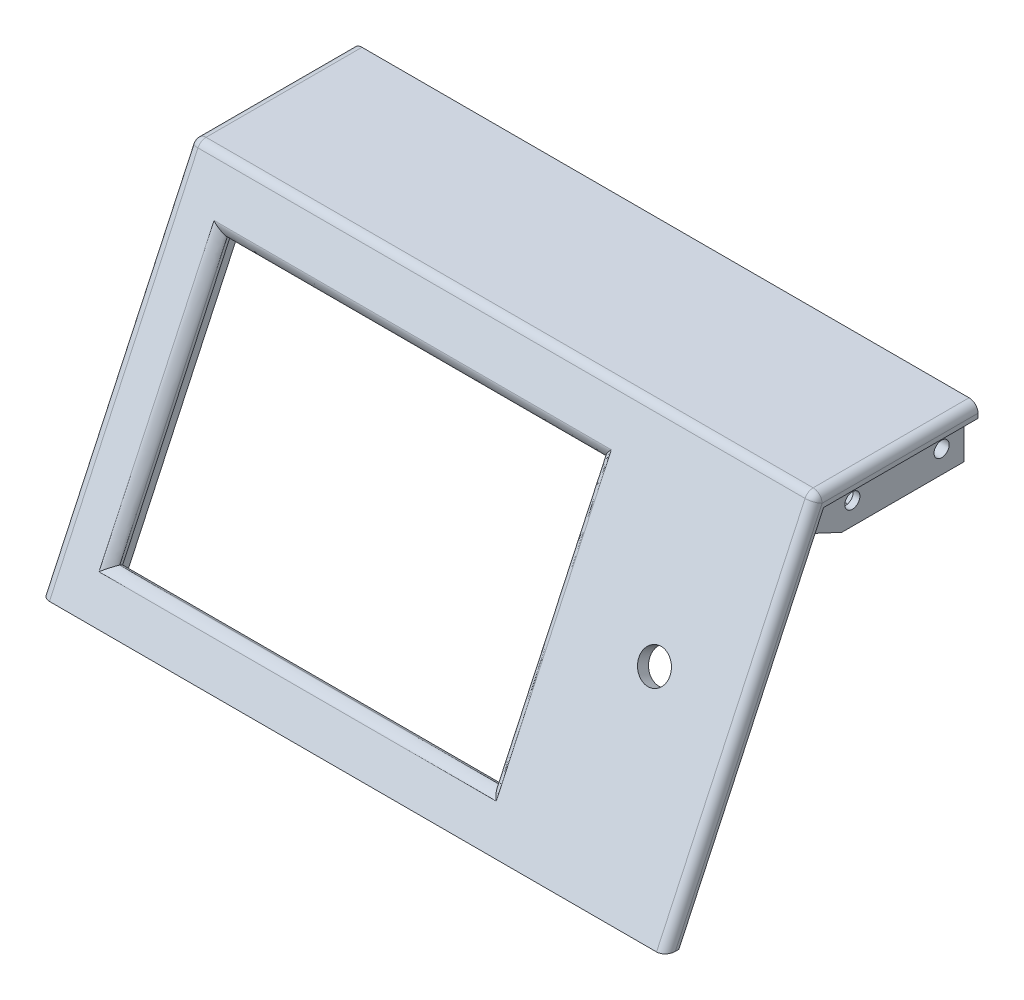
SolidWorks part; units mm, degrees
ref_plane "Piano frontale" through (0, 0, 0) normal (0, 0, 1) x (1, 0, 0)
ref_plane "Piano superiore" through (0, 0, 0) normal (0, 1, 0) x (1, 0, 0)
ref_plane "Piano destro" through (0, 0, 0) normal (1, 0, 0) x (0, 0, -1)
sketch "Schizzo5" plane through (0, 0, 0) normal (-1, 0, 0) x (0, 0, 1)
  line L0 (30.8095, -72.5046) -> (-3, 0)
  line L3 (33.8095, -72.5046) -> (30.8095, -72.5046)
  line L5 (-3, 0) -> (0, 0)
  line L6 (0, 0) -> (33.8095, -72.5046)
  line L7 (0, 0) -> (0, -3)
  line L8 (0, -3) -> (-36.2, -3)
  line L9 (-36.2, -3) -> (-36.2, 0)
  line L10 (-36.2, 0) -> (0, 0)
  dimension "D1" = 3
  dimension "D2" = 3
  dimension "D4" = 80
  dimension "D5" = 115
  dimension "D6" = 3
  dimension "D7" = 36.2
extrude "Estrusione-Estrusione3" add sketch "Schizzo5" against normal blind 140
sketch "Schizzo6" plane through (0, 0, 0) normal (0, 0.4226, 0.9063) x (1, 0, 0)
  line L0 (140, 0) -> (0, 0) construction
  line L1 (11.5, -69.5) -> (96.5, -69.5)
  line L2 (11.5, -69.5) -> (11.5, -12.5)
  line L3 (11.5, -12.5) -> (96.5, -12.5)
  line L4 (96.5, -69.5) -> (96.5, -12.5)
  line L5 (140, 0) -> (0, 0) construction
  line L6 (0, 0) -> (0, -80) construction
  line L7 (140, 0) -> (140, -80) construction
  circle A0 centre (120, -38.5) radius 3.5
  point P12 (11.5, -41)
  dimension "D5" = 7
  dimension "D7" = 20
  dimension "D1" = 85
  dimension "D2" = 57
  dimension "D3" = 41
  dimension "D4" = 11.5
  dimension "D6" = 38.5
extrude "Taglio-Estrusione1" cut sketch "Schizzo6" against normal up to next
fillet "Raccordo1" radius 2 4 edges at (96.5, -37.1586, 17.3273) (54, -62.9884, 29.372) (54, -11.3288, 5.2827) (11.5, -37.1586, 17.3273) conic rho 0.2
sketch "Schizzo8" plane through (0, -1.1491, -2.4642) normal (0, -0.4226, -0.9063) x (-1, 0, 0)
  line L0 (0, -78.7321) -> (0, -2.0423) construction
  line L1 (-114.2, -20.0423) -> (-104.2, -20.0423)
  line L2 (-114.2, -20.0423) -> (-114.2, -8.0423)
  line L3 (-114.2, -8.0423) -> (-104.2, -8.0423)
  line L4 (-104.2, -20.0423) -> (-104.2, -8.0423)
  line L5 (-96.5, -12.5) -> (-96.5, -69.5) construction
  line L7 (-114.2, -72.7321) -> (-104.2, -72.7321)
  line L8 (-114.2, -72.7321) -> (-114.2, -60.7321)
  line L9 (-114.2, -60.7321) -> (-104.2, -60.7321)
  line L10 (-104.2, -72.7321) -> (-104.2, -60.7321)
  line L11 (-11.5, -69.5) -> (-11.5, -12.5) construction
  line L12 (-3, -72.7321) -> (-9.8, -72.7321)
  line L13 (-3, -72.7321) -> (-3, -8.0423)
  line L14 (-3, -8.0423) -> (-9.8, -8.0423)
  line L15 (-9.8, -72.7321) -> (-9.8, -8.0423)
  line L17 (-140, -2.0423) -> (0, -2.0423) construction
  line L19 (-140, -78.7321) -> (0, -78.7321) construction
  dimension "D1" = 7.7
  dimension "D2" = 12
  dimension "D3" = 10
  dimension "D4" = 12
  dimension "D5" = 1.7
  dimension "D6" = 6
  dimension "D7" = 6
  dimension "D8" = 6
  dimension "D9" = 6
  dimension "D10" = 3
extrude "Estrusione-Estrusione4" add sketch "Schizzo8" along normal blind 4
sketch "Schizzo9" plane through (0, -1.1491, -2.4642) normal (0, -0.4226, -0.9063) x (-1, 0, 0)
  line L5 (-140, -78.7321) -> (0, -78.7321) construction
  line L6 (-125, -78.7321) -> (-18, -78.7321)
  line L7 (-125, -78.7321) -> (-125, -72.7321)
  line L8 (-125, -72.7321) -> (-18, -72.7321)
  line L9 (-18, -78.7321) -> (-18, -72.7321)
  line L10 (-3, -72.7321) -> (-3, -8.0423) construction
  line L12 (-140, -78.7321) -> (-140, -2.0423) construction
  point P12 (-18, -75.7321)
  dimension "D1" = 15
  dimension "D2" = 6
  dimension "D3" = 15
extrude "Estrusione-Estrusione5" add sketch "Schizzo9" along normal blind 6
sketch "Schizzo10" plane through (18, 0, 0) normal (-1, 0, 0) x (0, 0, 1)
  line L0 (30.8095, -72.5046) -> (26.1001, -74.7006)
  line L1 (25.3716, -75.0403) -> (30.8095, -72.5046) construction
  line L2 (26.1001, -74.7006) -> (29.5416, -69.7857)
  line L3 (29.5416, -69.7857) -> (30.8095, -72.5046)
  line L4 (25.3716, -75.0403) -> (22.8359, -69.6025) construction
  line L5 (30.8095, -72.5046) -> (28.2738, -67.0668) construction
  line L6 (28.2738, -67.0668) -> (24.2999, -72.742)
  line L7 (24.2999, -72.742) -> (22.8359, -69.6025)
  line L8 (22.8359, -69.6025) -> (28.2738, -67.0668)
  dimension "D1" = 3
  dimension "D2" = 60
extrude "Taglio-Estrusione2" cut sketch "Schizzo10" along direction (-1, 0, 0) on the side against the normal up to surface (107 mm away) and the other way through all from surface up to face at (125, -71.0536, 26.8227) starting at face at (18, -71.0536, 26.8227)
sketch "Schizzo12" plane through (0, -1.1491, -2.4642) normal (0, -0.4226, -0.9063) x (-1, 0, 0)
  line L1 (-132.2, -27.3) -> (-126.2, -27.3)
  line L2 (-132.2, -27.3) -> (-132.2, -46.3)
  line L3 (-132.2, -46.3) -> (-126.2, -46.3)
  line L4 (-126.2, -27.3) -> (-126.2, -46.3)
  circle A0 centre (-120, -38.5) radius 3.5 construction
  dimension "D1" = 11.2
  dimension "D2" = 6
  dimension "D3" = 6.2
  dimension "19" = 19
extrude "Estrusione-Estrusione6" add sketch "Schizzo12" along normal blind 4.5
fillet "Raccordo2" radius 2 5 edges at (0, 0, -18.1) (0, -36.2523, 16.9047) (140, -36.2523, 16.9047) (140, 0, -18.1) (70, 0, 0)
ref_plane "Piano1" through (136.85, 0, 0) normal (1, 0, 0) x (0, 0, -1)
sketch "Schizzo14" plane through (136.85, 0, 0) normal (1, 0, 0) x (0, 0, -1)
  line L0 (1.6011, -3) -> (-0.9346, -8.4378)
  line L1 (-30.8095, -72.5046) -> (1.6011, -3) construction
  line L4 (36.2, -13) -> (36.2, -3)
  line L5 (36.2, -3) -> (1.6011, -3)
  line L6 (-0.9346, -8.4378) -> (8.8489, -13)
  line L7 (8.8489, -13) -> (36.2, -13)
  dimension "D1" = 6
  dimension "D2" = 10
extrude "Estrusione-Estrusione7" add sketch "Schizzo14" against normal blind 4
ref_plane "Piano2" through (70, 0, 0) normal (-1, 0, 0) x (0, 0, 1)
mirror "Specchia1" about plane through (70, 0, 0) normal (-1, 0, 0) of "Estrusione-Estrusione7"
sketch "Schizzo15" plane through (0, -2.8395, -6.0894) normal (0, -0.4226, -0.9063) x (-1, 0, 0)
  line L0 (-114.2, -8.0423) -> (-114.2, -20.0423) construction
  line L1 (-104.2, -8.0423) -> (-114.2, -8.0423) construction
  circle A0 centre (-108.2, -13.5423) radius 1
  circle A1 centre (-108.2, -69.3423) radius 0.75
  circle A2 centre (-6.8, -13.5423) radius 1
  circle A4 centre (-6.8, -69.3423) radius 0.75
  dimension "D1" = 2
  dimension "D2" = 6
  dimension "D3" = 5.5
  dimension "D4" = 1.5
  dimension "D5" = 2
  dimension "D6" = 1.5
  dimension "D9" = 55.8
  dimension "D7" = 101.4
extrude "Taglio-Estrusione3" cut sketch "Schizzo15" against normal blind 5 contours A0 | A1 | A4 | A2 region at (108.2, -15.113, -0.3662) region at (108.2, -65.685, 23.2159)
sketch "Schizzo16" plane through (0, -3.0508, -6.5426) normal (0, -0.4226, -0.9063) x (-1, 0, 0)
  circle A0 centre (-128.25, -29.75) radius 0.75
  circle A1 centre (-128.25, -43.75) radius 0.75
  dimension "D1" = 1.5
  dimension "D2" = 1.5
extrude "Taglio-Estrusione4" cut sketch "Schizzo16" against normal blind 5
sketch "Schizzo18" plane through (136.85, 0, 0) normal (1, 0, 0) x (0, 0, -1)
  line L0 (36.2, -13) -> (36.2, -3) construction
  line L1 (1.6011, -3) -> (36.2, -3) construction
  circle A0 centre (11.2, -8) radius 1.7
  circle A1 centre (31.2, -8) radius 1.7
  dimension "D1" = 3.4
  dimension "D2" = 3.4
  dimension "D4" = 5
  dimension "D5" = 5
  dimension "D3" = 20
extrude "Taglio-Estrusione5" cut sketch "Schizzo18" against normal through all contours A0 | A1 region at (136.85, -8, -11.2) region at (136.85, -8, -31.2)
sketch "Schizzo20" plane through (7.15, 0, 0) normal (1, 0, 0) x (0, 0, -1)
  line L0 (8.8489, -13) -> (36.2, -13) construction
  line L1 (12.8454, -5.15) -> (9.5546, -5.15)
  line L2 (9.5546, -5.15) -> (7.9091, -8)
  line L3 (7.9091, -8) -> (9.5546, -10.85)
  line L4 (9.5546, -10.85) -> (12.8454, -10.85)
  line L5 (12.8454, -10.85) -> (14.4909, -8)
  line L6 (14.4909, -8) -> (12.8454, -5.15)
  circle A0 centre (11.2, -8) radius 2.85 construction
  point P1 (11.2, -5.15)
  dimension "D1" = 5.7
extrude "Taglio-Estrusione6" cut sketch "Schizzo20" against normal blind 2.5
sketch "Schizzo21" plane through (132.85, 0, 0) normal (-1, 0, 0) x (0, 0, 1)
  line L0 (-8.8489, -13) -> (-36.2, -13) construction
  line L2 (-9.5546, -5.15) -> (-12.8454, -5.15)
  line L3 (-12.8454, -5.15) -> (-14.4909, -8)
  line L4 (-14.4909, -8) -> (-12.8454, -10.85)
  line L5 (-12.8454, -10.85) -> (-9.5546, -10.85)
  line L6 (-9.5546, -10.85) -> (-7.9091, -8)
  line L7 (-7.9091, -8) -> (-9.5546, -5.15)
  circle A0 centre (-11.2, -8) radius 2.85 construction
  dimension "D1" = 5.7
extrude "Taglio-Estrusione7" cut sketch "Schizzo21" against normal blind 2.5
